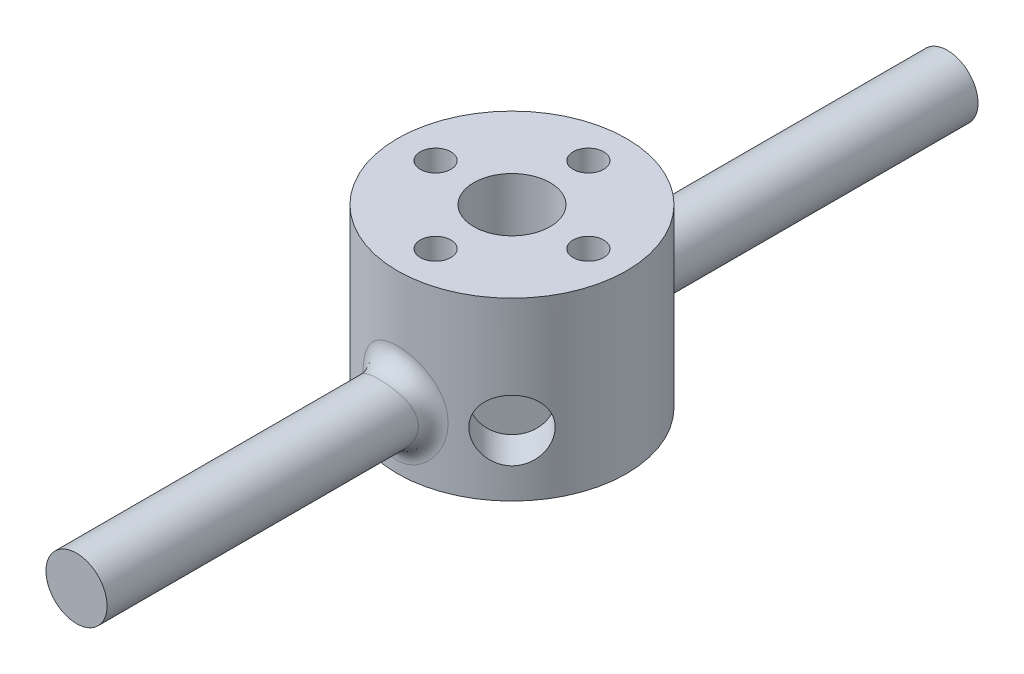
SolidWorks part; units mm, degrees
ref_plane "Front Plane" through (0, 0, 0) normal (0, 0, 1) x (1, 0, 0)
ref_plane "Top Plane" through (0, 0, 0) normal (0, 1, 0) x (1, 0, 0)
ref_plane "Right Plane" through (0, 0, 0) normal (1, 0, 0) x (0, 0, -1)
sketch "Sketch2" plane through (0, 0, 0) normal (0, 1, 0) x (1, 0, 0)
  circle A0 centre (0, 0) radius 15
  dimension "D1" = 30
extrude "Boss-Extrude1" add sketch "Sketch2" along normal blind 30
sketch "Sketch3" plane through (0, 0, 0) normal (0, -1, 0) x (1, 0, 0)
  circle A0 centre (0, 0) radius 5
  dimension "D1" = 10
extrude "Cut-Extrude1" cut sketch "Sketch3" against normal blind 37
sketch "Sketch4" plane through (0, 30, 0) normal (0, 1, 0) x (1, 0, 0)
  circle A0 centre (0, 0) radius 5 construction
  circle A1 centre (0, 10) radius 2
  circle A3 centre (0, 0) radius 15 construction
  dimension "D1" = 4
  dimension "D2" = 10
extrude "Cut-Extrude2" cut sketch "Sketch4" against normal blind 15
sketch "Sketch6" plane through (0, 30, 0) normal (0, 1, 0) x (1, 0, 0)
  line L0 (0, 0) -> (0, 6.2754) construction
pattern_circular "CirPattern2" count 4 over 360 about axis through (0, 30, 0) along (0, 1, 0) of "Cut-Extrude2"
sketch "Sketch7" plane through (0, 30, 0) normal (0, 1, 0) x (1, 0, 0)
ref_plane "Plane2" through (0, 0, 15) normal (0, 0, 1) x (1, 0, 0)
sketch "Sketch11" plane through (0, 0, 15) normal (0, 0, 1) x (1, 0, 0)
  line L0 (-15, 15) -> (15, 15) construction
  line L1 (-15, 30) -> (-15, 0) construction
  line L2 (15, 0) -> (15, 30) construction
  circle A0 centre (0, 15) radius 4
  dimension "D1" = 8
extrude "Boss-Extrude3" add sketch "Sketch11" along normal blind 42 and the other way blind 2 contours A0
mirror "Mirror1" about plane through (0, 0, 0) normal (0, 0, 1) of "Boss-Extrude3"
sketch "Sketch14" plane through (0, 0, 0) normal (0, -1, 0) x (1, 0, 0)
  circle A0 centre (0, 0) radius 15
extrude "Cut-Extrude3" cut sketch "Sketch14" against normal blind 7
fillet "Fillet8" radius 6 1 edges at (0, 7, -5) conic rho 0.05
sketch "Sketch15" plane through (0, 7, 0) normal (0, -1, 0) x (1, 0, 0)
  line L0 (0, 15) -> (0, 11) construction
  circle A0 centre (0, 0) radius 15 construction
  spline S0 degree 3 poles (-2.1596, -10.8569) (0, -11.0716) (2.1596, -10.8569) (4.2369, -10.2288) (6.1499, -9.204) (7.8288, -7.8288) (9.204, -6.1499) (10.2288, -4.2369) (10.8569, -2.1596) (11.0716, 0) (10.8569, 2.1596) (10.2288, 4.2369) (9.204, 6.1499) (7.8288, 7.8288) (6.1499, 9.204) (4.2369, 10.2288) (2.1596, 10.8569) (0, 11.0716) (-2.1596, 10.8569) (-4.2369, 10.2288) (-6.1499, 9.204) (-7.8288, 7.8288) (-9.204, 6.1499) (-10.2288, 4.2369) (-10.8569, 2.1596) (-11.0716, 0) (-10.8569, -2.1596) (-10.2288, -4.2369) (-9.204, -6.1499) (-7.8288, -7.8288) (-6.1499, -9.204) (-4.2369, -10.2288) (-2.1596, -10.8569) (0, -11.0716) (2.1596, -10.8569) knots -0.09375 -0.0625 -0.03125 0 0.03125 0.0625 0.09375 0.125 0.15625 0.1875 0.21875 0.25 0.28125 0.3125 0.34375 0.375 0.40625 0.4375 0.46875 0.5 0.53125 0.5625 0.59375 0.625 0.65625 0.6875 0.71875 0.75 0.78125 0.8125 0.84375 0.875 0.90625 0.9375 0.96875 1 1.03125 1.0625 1.09375 only from (0, -11) to (0, -11) construction
  dimension "D1" = 4
ref_plane "Plane4" through (10.6066, 0, 10.6066) normal (0.7071, 0, 0.7071) x (0, -1, 0)
sketch "Sketch16" plane through (10.6066, 0, 10.6066) normal (0.7071, 0, 0.7071) x (0, -1, 0)
  line L0 (-15, 43.1335) -> (-15, -43.1335) construction
  line L1 (-85.0856, 0) -> (25.6119, 0) construction
  circle A0 centre (-15, 0) radius 4
  ellipse E0 centre (-15, 40.3051) end of major axis (-19, 40.3051) minor radius 2.8284 construction
  ellipse E1 centre (-15, -40.3051) end of major axis (-19, -40.3051) minor radius 2.8284 construction
extrude "Cut-Extrude4" cut sketch "Sketch16" against normal blind 5
ref_plane "Plane5" through (0, 0, 0) normal (-0.7071, 0, -0.7071) x (0, -1, 0)
mirror "Mirror2" about plane through (0, 0, 0) normal (-0.7071, 0, -0.7071) of "Cut-Extrude4"
fillet "Fillet9" radius 2.5 1 edges at (-0.7639, 11.0736, -14.9805)
fillet "Fillet10" radius 2.5 1 edges at (-3.9261, 15.7653, 14.4771)
sketch "Sketch17" plane through (0, 0, -57) normal (0, 0, -1) x (-1, 0, 0)
  line L0 (0, 19) -> (0, 11) construction
  line L1 (0, 15) -> (0, 7) construction
  line L2 (-11, 7) -> (11, 7) construction
  circle A0 centre (0, 15) radius 4 construction
  circle A1 centre (0, 15) radius 4 construction
  dimension "D1" = 8
